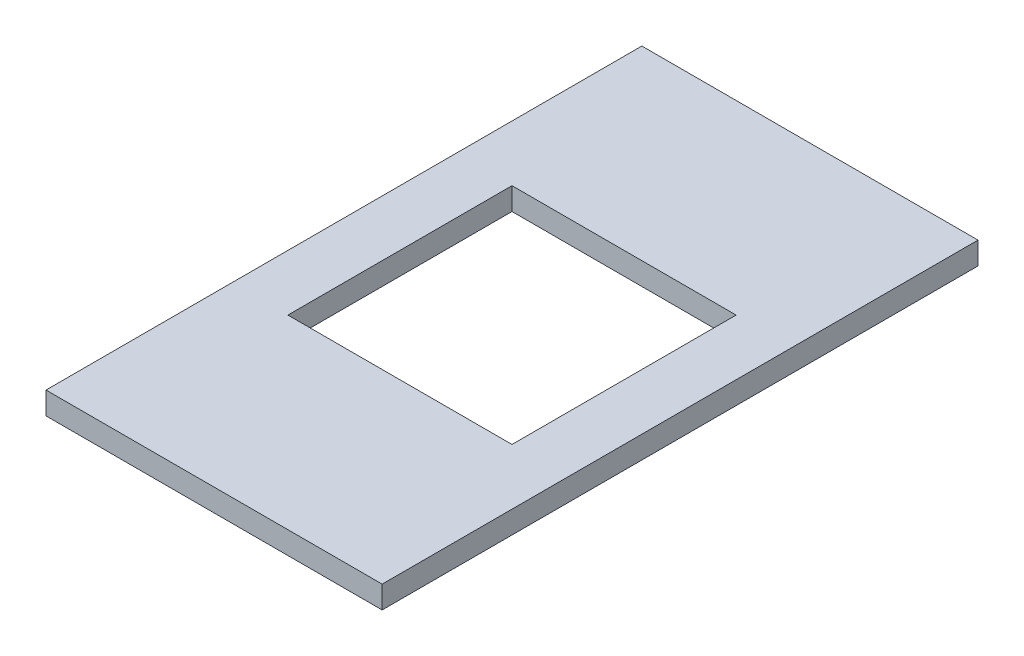
SolidWorks part; units mm, degrees
ref_plane "Front Plane" through (0, 0, 0) normal (0, 0, 1) x (1, 0, 0)
ref_plane "Top Plane" through (0, 0, 0) normal (0, 1, 0) x (1, 0, 0)
ref_plane "Right Plane" through (0, 0, 0) normal (1, 0, 0) x (0, 0, -1)
sketch "Sketch1" plane through (0, 0, 0) normal (0, 1, 0) x (1, 0, 0)
  line L1 (0, 0) -> (-150, 0)
  line L2 (0, 0) -> (0, 30)
  line L3 (0, 30) -> (-150, 30)
  line L4 (-150, 0) -> (-150, 30)
  dimension "D1" = 30
  dimension "D2" = 150
extrude "Boss-Extrude1" add sketch "Sketch1" along normal blind 10
sketch "Sketch8" plane through (0, 0, 0) normal (0, -1, 0) x (-1, 0, 0)
  line L0 (150, 0) -> (0, 30)
  line L1 (150, 30) -> (0, 0)
  line L2 (150, 0) -> (0, 0) construction
sketch "Sketch9" plane through (0, 0, 0) normal (0, -1, 0) x (1, 0, 0)
  line L0 (-150, -30) -> (0, 0) construction
  line L1 (0, -147.94) -> (-150, -147.94)
  line L2 (0, -147.94) -> (0, 117.94)
  line L3 (0, 117.94) -> (-150, 117.94)
  line L4 (-150, -147.94) -> (-150, 117.94)
  line L5 (0, -147.94) -> (-150, 117.94) construction
  line L6 (0, 117.94) -> (-150, -147.94) construction
  line L8 (-125, -65) -> (-25, -65)
  line L9 (-125, -65) -> (-125, 35)
  line L10 (-125, 35) -> (-25, 35)
  line L11 (-25, -65) -> (-25, 35)
  line L12 (-125, -65) -> (-25, 35) construction
  line L13 (-125, 35) -> (-25, -65) construction
  point P0 (-75, -15)
  point P7 (-75, -15)
  point P12 (-75, 117.94)
  point P13 (-75, -147.94)
  dimension "D1" = 265.88
  dimension "D2" = 150
  dimension "D3" = 100
  dimension "D4" = 100
extrude "Boss-Extrude3" add sketch "Sketch9" along normal blind 10
sketch "Sketch25" plane through (0, 0, 0) normal (0, 1, 0) x (1, 0, 0)
  line L1 (0, 30) -> (-150, 30)
  line L2 (0, 30) -> (0, 0)
  line L3 (0, 0) -> (-150, 0)
  line L4 (-150, 30) -> (-150, 0)
extrude "Cut-Extrude2" cut sketch "Sketch25" along normal blind 10
sketch "Alignment Sketch" plane through (0, 0, 0) normal (0, 1, 0) x (1, 0, 0)
  line L0 (-150, 147.94) -> (0, 147.94) construction
  line L1 (0, 147.94) -> (0, -117.94) construction
  point P0 (-75, 147.94)
  point P1 (0, 15)
sketch "Alignment Sketch 2" plane through (0, 0, -147.94) normal (0, 0, -1) x (-1, 0, 0)
  line L0 (75, 0) -> (75, -10) construction
  line L1 (150, -10) -> (0, -10) construction
